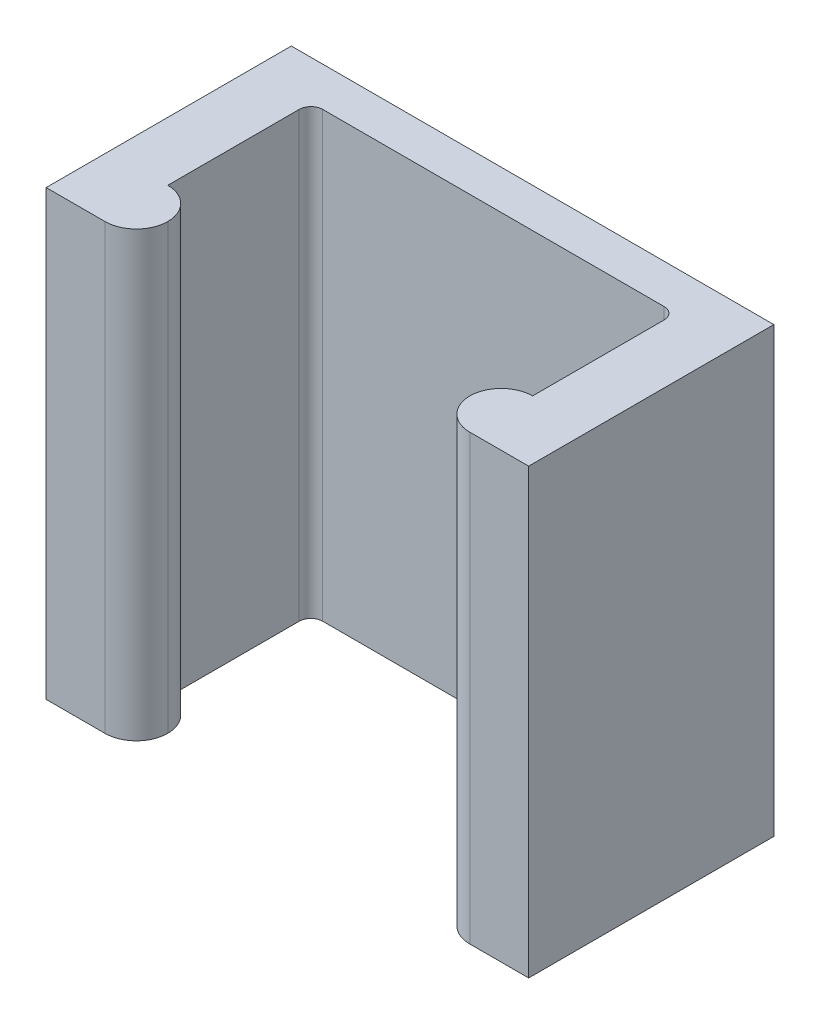
SolidWorks part; units mm, degrees
ref_plane "정면" through (0, 0, 0) normal (0, 0, 1) x (1, 0, 0)
ref_plane "윗면" through (0, 0, 0) normal (0, 1, 0) x (1, 0, 0)
ref_plane "우측면" through (0, 0, 0) normal (1, 0, 0) x (0, 0, -1)
sketch "스케치1" plane through (0, 0, 0) normal (0, 0, 1) x (1, 0, 0)
  line L1 (-6.15, -5.65) -> (6.15, -5.65)
  line L2 (-6.15, -5.65) -> (-6.15, 5.65)
  line L3 (-6.15, 5.65) -> (6.15, 5.65)
  line L4 (6.15, -5.65) -> (6.15, 5.65)
  line L5 (-6.15, -5.65) -> (6.15, 5.65) construction
  line L6 (-6.15, 5.65) -> (6.15, -5.65) construction
  point P0 (0, 0)
  dimension "D1" = 12.3
  dimension "D2" = 11.3
extrude "보스-돌출1" add sketch "스케치1" along normal blind 2
sketch "스케치2" plane through (0, 0, 2) normal (0, 0, 1) x (1, 0, 0)
  line L0 (-6.15, -5.65) -> (6.15, -5.65) construction
  line L1 (-6.15, 5.65) -> (-4.65, 5.65)
  line L2 (-6.15, 5.65) -> (-6.15, -5.65)
  line L3 (-6.15, -5.65) -> (-4.65, -5.65)
  line L4 (-4.65, 5.65) -> (-4.65, -5.65)
  line L6 (6.15, 5.65) -> (4.65, 5.65)
  line L7 (6.15, 5.65) -> (6.15, -5.65)
  line L8 (6.15, -5.65) -> (4.65, -5.65)
  line L9 (4.65, 5.65) -> (4.65, -5.65)
  dimension "D1" = 1.5
  dimension "D2" = 1.5
extrude "보스-돌출2" add sketch "스케치2" along normal blind 4.25
sketch "스케치5" plane through (0, 0, 2) normal (0, 0, 1) x (1, 0, 0)
  line L0 (4.65, 5.65) -> (4.65, -5.65) construction
  line L1 (-4.65, -5.75) -> (4.65, -5.75)
  line L2 (-4.65, -5.75) -> (-4.65, 5.75)
  line L3 (-4.65, 5.75) -> (4.65, 5.75)
  line L4 (4.65, -5.75) -> (4.65, 5.75)
  line L5 (-4.65, -5.75) -> (4.65, 5.75) construction
  line L6 (-4.65, 5.75) -> (4.65, -5.75) construction
  point P0 (0, 0)
  dimension "D1" = 11.5
extrude "컷-돌출1" cut sketch "스케치5" against normal blind 1
sketch "스케치8" plane through (-4.65, 0, 0) normal (1, 0, 0) x (0, 0, -1)
  line L0 (-6.25, -5.65) -> (-1, -5.65) construction
  line L1 (-6.25, 5.65) -> (-4.65, 5.65)
  line L2 (-6.25, 5.65) -> (-6.25, -5.65)
  line L3 (-6.25, -5.65) -> (-4.65, -5.65)
  line L4 (-4.65, 5.65) -> (-4.65, -5.65)
  dimension "D1" = 1.6
extrude "보스-돌출5" add sketch "스케치8" along normal blind 0.8
sketch "스케치9" plane through (4.65, 0, 0) normal (-1, 0, 0) x (0, 0, 1)
  line L0 (6.25, 5.65) -> (1, 5.65) construction
  line L1 (6.25, -5.65) -> (4.65, -5.65)
  line L2 (6.25, -5.65) -> (6.25, 5.65)
  line L3 (6.25, 5.65) -> (4.65, 5.65)
  line L4 (4.65, -5.65) -> (4.65, 5.65)
  dimension "D1" = 1.6
extrude "보스-돌출6" add sketch "스케치9" along normal blind 0.8
fillet "필렛7" radius 0.8 4 edges at (3.85, 0, 6.25) (-3.85, 0, 6.25) (3.85, 0, 4.65) (-3.85, 0, 4.65)
fillet "필렛8" radius 0.3 2 edges at (4.65, 0, 1) (-4.65, 0, 1)
